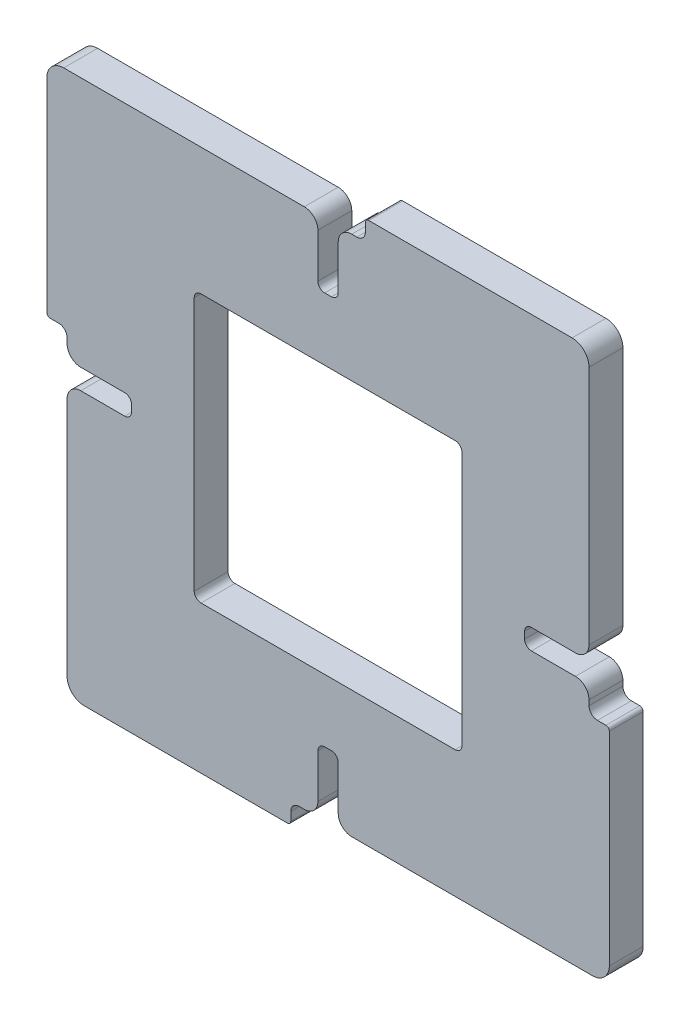
SolidWorks part; units mm, degrees
ref_plane "front" through (0, 0, 0) normal (0, 0, 1) x (1, 0, 0)
ref_plane "top" through (0, 0, 0) normal (0, 1, 0) x (1, 0, 0)
ref_plane "right" through (0, 0, 0) normal (1, 0, 0) x (0, 0, -1)
ref_axis "Axis1" through (0, 0, -69.7337) along (0, 0, 1)
sketch "Sketch1" plane through (0, 0, 0) normal (0, 0, 1) x (1, 0, 0)
  line L0 (-1.9558, 1.9558) -> (1.9558, 1.9558)
  line L1 (1.9558, 1.9558) -> (1.9558, -1.9558)
  line L2 (1.9558, -1.9558) -> (-1.9558, -1.9558)
  line L3 (-1.9558, -1.9558) -> (-1.9558, 1.9558)
  line L4 (-1.9558, 0) -> (-22.3549, 0) construction
  line L5 (-22.3549, 0) -> (0, 3.9418)
  line L6 (-22.3549, 0) -> (0, 1.9558)
  line L7 (-22.3549, 0) -> (0, 3.0424)
  dimension "D1" = 10
  dimension "D2" = 5
  dimension "D3" = 22.3549
  dimension "D4" = 22.6998
  dimension "D5" = 2.25
sketch "Sketch2" plane through (0, 0, 0) normal (0, 0, 1) x (1, 0, 0)
  line L1 (-0.1524, 3.7084) -> (-0.1524, 3.048)
  line L2 (0.6096, 4.2164) -> (3.6576, 4.2164)
  line L4 (2.0066, 0.762) -> (3.9116, 0.762)
  line L5 (3.9116, 0.762) -> (3.9116, 3.9624)
  line L6 (0.4318, 3.9116) -> (0.3556, 3.9116)
  line L7 (0, 4.1205) -> (0, 6.0044) construction
  line L8 (0.1524, 3.7084) -> (0.1524, 3.048)
  line L9 (-0.3556, 3.9116) -> (-0.889, 3.9116)
  line L10 (0.5588, 4.1656) -> (0.5588, 4.0386)
  line L14 (0.0508, 2.9464) -> (-0.0508, 2.9464)
  line L15 (-0.889, 3.9116) -> (-0.889, 2.0066)
  line L16 (-0.889, 2.0066) -> (1.905, 2.0066)
  line L24 (-1.9558, 1.9558) -> (1.9558, 1.9558) construction
  line L25 (1.9558, 1.9558) -> (1.9558, -1.9558) construction
  line L26 (2.0066, 1.905) -> (2.0066, 0.762)
  arc A0 (0.1524, 3.048) -> (0.0508, 2.9464) centre (0.0508, 3.048) cw
  arc A1 (-0.1524, 3.048) -> (-0.0508, 2.9464) centre (-0.0508, 3.048) ccw
  arc A2 (3.6576, 4.2164) -> (3.9116, 3.9624) centre (3.6576, 3.9624) cw
  arc A3 (0.3556, 3.9116) -> (0.1524, 3.7084) centre (0.3556, 3.7084) ccw
  arc A4 (-0.3556, 3.9116) -> (-0.1524, 3.7084) centre (-0.3556, 3.7084) cw
  circle A5 centre (0, 0) radius 1.6256 construction
  arc A6 (1.905, 2.0066) -> (2.0066, 1.905) centre (1.905, 1.905) cw
  arc A9 (0.5588, 4.0386) -> (0.4318, 3.9116) centre (0.4318, 4.0386) cw
  arc A10 (0.6096, 4.2164) -> (0.5588, 4.1656) centre (0.6096, 4.1656) ccw
  point P29 (0.1524, 3.9116)
  dimension "D3" = 0.254
  dimension "D14" = 0.0508
  dimension "D6" = 0.1016
  dimension "D2" = 3.9116
  dimension "D7" = 0.1016
  dimension "D11" = 0.2032
  dimension "D8" = 3.2512
  dimension "D19" = 0.0302
  dimension "D20" = 0.127
  dimension "D21" = 0.0508
  dimension "D4" = 2.9464
  dimension "D5" = 0.3048
  dimension "D12" = 0.0508
  dimension "D13" = 0.762
  dimension "D15" = 3.9116
  dimension "D22" = 0.3048
  dimension "D23" = 0.5588
  dimension "D29" = 0.889
extrude "Extrude1" add sketch "Sketch2" against normal mid plane 0.508
pattern_circular "CirPattern1" count 4 over 360 about axis through (0, 0, -69.7337) along (0, 0, 1) of "Extrude1"
